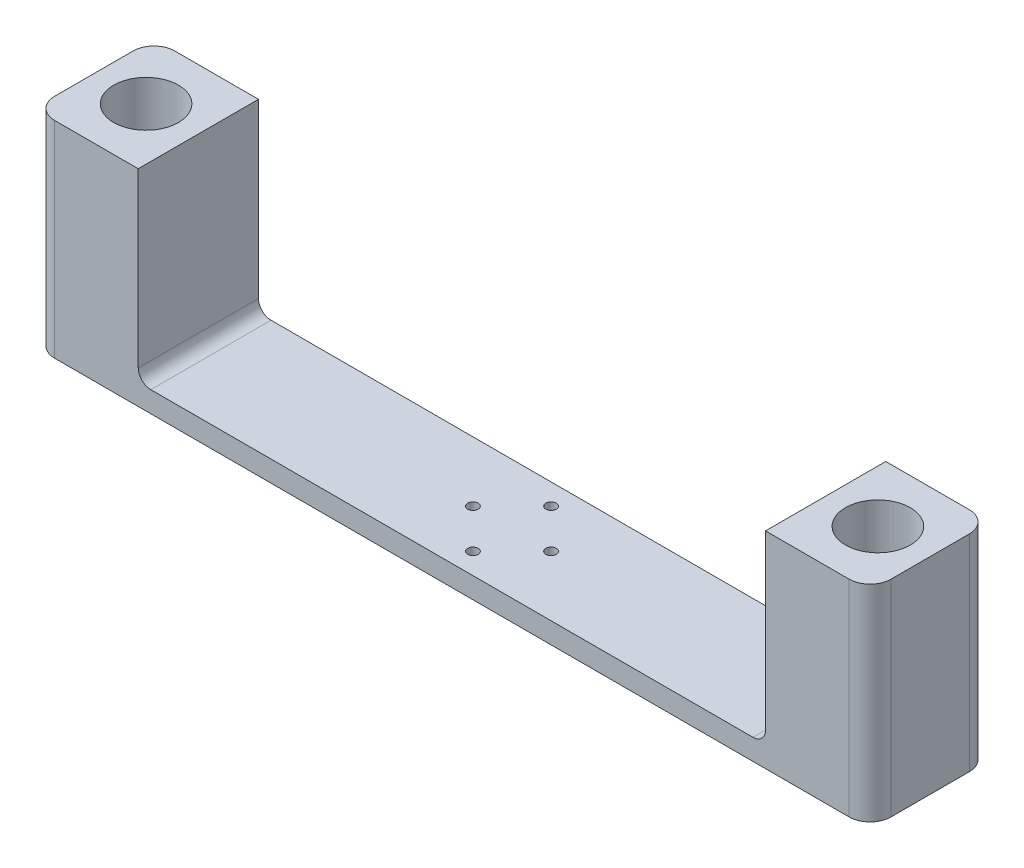
SolidWorks part; units mm, degrees
ref_plane "Front Plane" through (0, 0, 0) normal (0, 0, 1) x (1, 0, 0)
ref_plane "Top Plane" through (0, 0, 0) normal (0, 1, 0) x (1, 0, 0)
ref_plane "Right Plane" through (0, 0, 0) normal (1, 0, 0) x (0, 0, -1)
sketch "Sketch1" plane through (0, 0, 0) normal (0, 1, 0) x (1, 0, 0)
  line L0 (0, 0) -> (0, 4.9523) construction
  line L1 (0, 4.9523) -> (0, 0) construction
  line L2 (0, 0) -> (2.8355, 0) construction
  circle A0 centre (0, 0) radius 13.97
  circle A2 centre (0, 9.5) radius 1.275
  circle A3 centre (9.5, 0) radius 1.275
  circle A4 centre (0, -9.5) radius 1.275
  circle A5 centre (-9.5, 0) radius 1.275
  dimension "D2" = 27.94
  dimension "D3" = 2.55
extrude "Boss-Extrude1" add sketch "Sketch1" along normal blind 3.048
sketch "Sketch2" plane through (0, 3.048, 0) normal (0, 1, 0) x (1, 0, 0)
  line L1 (-96.52, -14.605) -> (96.52, -14.605)
  line L2 (-101.6, -9.525) -> (-101.6, 9.525)
  line L3 (-96.52, 14.605) -> (96.52, 14.605)
  line L4 (101.6, -9.525) -> (101.6, 9.525)
  line L5 (-101.6, -14.605) -> (101.6, 14.605) construction
  line L6 (-101.6, 14.605) -> (101.6, -14.605) construction
  circle A0 centre (-88.9, 0) radius 7.874
  circle A1 centre (88.9, 0) radius 7.874
  arc A3 (96.52, 14.605) -> (101.6, 9.525) centre (96.52, 9.525) cw
  arc A4 (96.52, -14.605) -> (101.6, -9.525) centre (96.52, -9.525) ccw
  arc A5 (-96.52, -14.605) -> (-101.6, -9.525) centre (-96.52, -9.525) cw
  arc A6 (-101.6, 9.525) -> (-96.52, 14.605) centre (-96.52, 9.525) cw
  circle A7 centre (9.5, 0) radius 1.275 construction
  circle A8 centre (0, 9.5) radius 1.275 construction
  circle A9 centre (-9.5, 0) radius 1.275 construction
  circle A10 centre (0, -9.5) radius 1.275 construction
  circle A11 centre (9.5, 0) radius 1.275
  circle A12 centre (0, 9.5) radius 1.275
  circle A13 centre (-9.5, 0) radius 1.275
  circle A14 centre (0, -9.5) radius 1.275
  point P0 (0, 0)
  dimension "D2" = 15.748
  dimension "D3" = 15.748
  dimension "D8" = 5.08
  dimension "D1" = 29.21
  dimension "D4" = 88.9
  dimension "D6" = 12.7
  dimension "D7" = 12.7
extrude "Boss-Extrude2" add sketch "Sketch2" along normal blind 46.99 and the other way through all
sketch "Sketch5" plane through (0, 0, -14.605) normal (0, 0, -1) x (-1, 0, 0)
  line L0 (-101.6, 0) -> (-101.6, 50.038)
  line L1 (-101.6, 50.038) -> (-76.2, 50.038)
  line L2 (-96.52, 50.038) -> (96.52, 50.038) construction
  line L3 (-76.2, 50.038) -> (-76.2, 5.08)
  line L4 (-76.2, 5.08) -> (76.2, 5.08)
  line L5 (0, 5.08) -> (0, 0)
  line L6 (101.6, 0) -> (-101.6, 0)
  line L7 (76.2, 50.038) -> (76.2, 5.08)
  line L8 (101.6, 50.038) -> (76.2, 50.038)
  line L9 (101.6, 0) -> (101.6, 50.038)
  line M8 (96.52, 50.038) -> (-96.52, 50.038)
  dimension "D1" = 25.4
  dimension "D2" = 5.08
extrude "Cut-Extrude2" cut sketch "Sketch5" against normal through all contours L7 L3 L4 M8 region at (0, 27.559, -14.605)
sketch "Sketch6" plane through (0, 0, 0) normal (0, -1, 0) x (1, 0, 0)
  circle A0 centre (-88.9, 0) radius 8.89
  circle A1 centre (-88.9, 0) radius 4.191
  circle A2 centre (88.9, 0) radius 8.89
  circle A3 centre (88.9, 0) radius 4.191
  dimension "D1" = 8.382
  dimension "D2" = 8.382
extrude "Boss-Extrude3" add sketch "Sketch6" against normal blind 4.572
fillet "Fillet2" radius 3.048 2 edges at (76.2, 5.08, 0) (-76.2, 5.08, 0)
